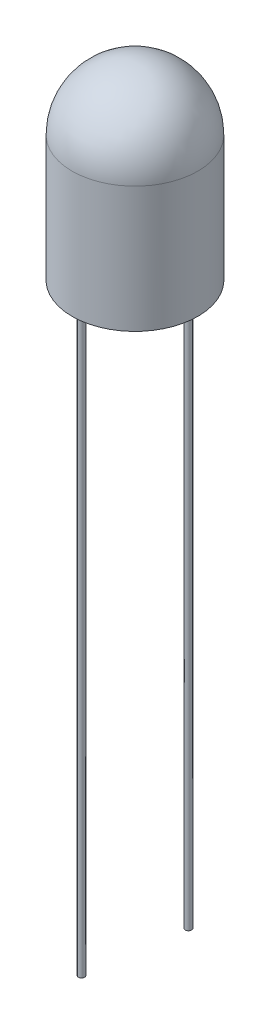
SolidWorks part; units mm, degrees
ref_plane "Front Plane" through (0, 0, 0) normal (0, 0, 1) x (1, 0, 0)
ref_plane "Top Plane" through (0, 0, 0) normal (0, 1, 0) x (1, 0, 0)
ref_plane "Right Plane" through (0, 0, 0) normal (1, 0, 0) x (0, 0, -1)
sketch "Sketch1" plane through (0, 0, 0) normal (0, 0, 1) x (1, 0, 0)
  line L0 (0, 4.375) -> (0, -0.6766) construction
  line L1 (0, 0) -> (1, 0)
  line L2 (1, 0) -> (1, 2)
  line L3 (0, 0) -> (0, 3)
  arc A0 (1, 2) -> (0, 3) centre (0, 2) ccw
  dimension "D1" = 1
  dimension "D2" = 2
revolve "Revolve1" add sketch "Sketch1" angle 360 about L0
sketch "Sketch2" plane through (0, 0, 0) normal (0, -1, 0) x (1, 0, 0)
  circle A0 centre (0.85, 0) radius 0.05
  circle A1 centre (-0.85, 0) radius 0.05
  dimension "D1" = 0.1
  dimension "D2" = 0.1
  dimension "D3" = 0.85
  dimension "D4" = 0.85
extrude "Boss-Extrude1" add sketch "Sketch2" along normal blind 10 contours A1 region at (-0.85, 0, 0)
extrude "Boss-Extrude2" add sketch "Sketch2<3>" along normal blind 8.5 contours A0 region at (0.85, 0, 0)
sketch "Sketch2<3>" plane through (0, 0, 0) normal (0, -1, 0) x (1, 0, 0) same geometry as "Sketch2"
